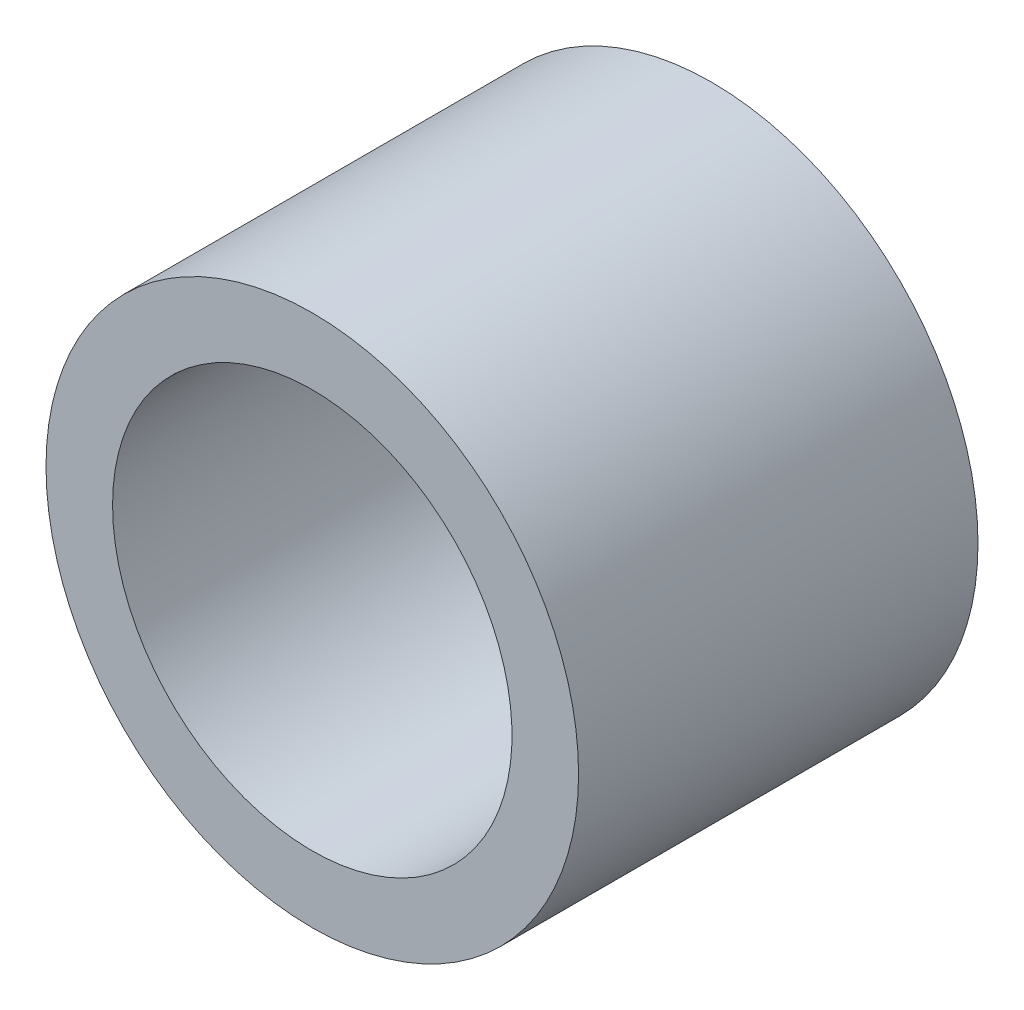
SolidWorks part; units mm, degrees
material "Tin Bearing Bronze"
ref_plane "Front Plane" through (0, 0, 0) normal (0, 0, 1) x (1, 0, 0)
ref_plane "Top Plane" through (0, 0, 0) normal (0, 1, 0) x (1, 0, 0)
ref_plane "Right Plane" through (0, 0, 0) normal (1, 0, 0) x (0, 0, -1)
sketch "Sketch1" plane through (0, 0, 0) normal (0, 0, 1) x (1, 0, 0)
  circle A0 centre (0, 0) radius 4.7625
  circle A1 centre (0, 0) radius 6.35
  dimension "D1" = 9.525
  dimension "D2" = 12.7
extrude "Boss-Extrude1" add sketch "Sketch1" along normal blind 9.525
equation "\"dovetail-angle\" = 60"
equation "\"dovetail-stock-width\" = 5"
equation "\"dovetail-stock-height\" = 1.25"
equation "\"dovetail-depth\" = 0.5 * \"dovetail-stock-height\""
equation "\"dovetail-throat-width\" = \"dovetail-stock-width\" - (2 * \"dovetail-depth\")"
equation "\"delta-x\" = 6"
equation "\"delta-y\" = 3"
equation "\"delta-z\"= 2.5"
equation "\"gib-thickness\" = 0.25"
equation "\"x-slide-length\" = \"dovetail-stock-width\" + \"delta-x\""
equation "\"y-slide-length\" = \"dovetail-stock-width\" + \"delta-y\""
equation "\"dog-point-diam\" = .149"
equation "\"dog-point-length\" = .067"
equation "\"dovetail-double-height\" = 2 * \"dovetail-depth\" + 0.5"
equation "\"acme-major-diam\" = .5"
equation "\"acme-pitch-diam\" = 0.45"
equation "\"acme-minor-diam\" = 0.4"
equation "\"x-screw-length\" = \"x-slide-length\" + \"screw-add-length\""
equation "\"y-screw-length\" = \"y-slide-length\" + \"screw-add-length\""
equation "\"acme-nut-od\" = 1.47"
equation "\"acme-nut-length\" = 1"
equation "\"acme-nut-trim-height\" = .75"
equation "\"screw-bearing-od\" = 0.5"
equation "\"screw-bearing-length\" = .375"
equation "\"end-plate-thickness\" = \"screw-bearing-length\""
equation "\"screw-bearing-id\" = .375"
equation "\"D1@Sketch1\"=\"screw-bearing-id\""
equation "\"D2@Sketch1\"=\"screw-bearing-od\""
equation "\"D1@Boss-Extrude1\"=\"screw-bearing-length\""
